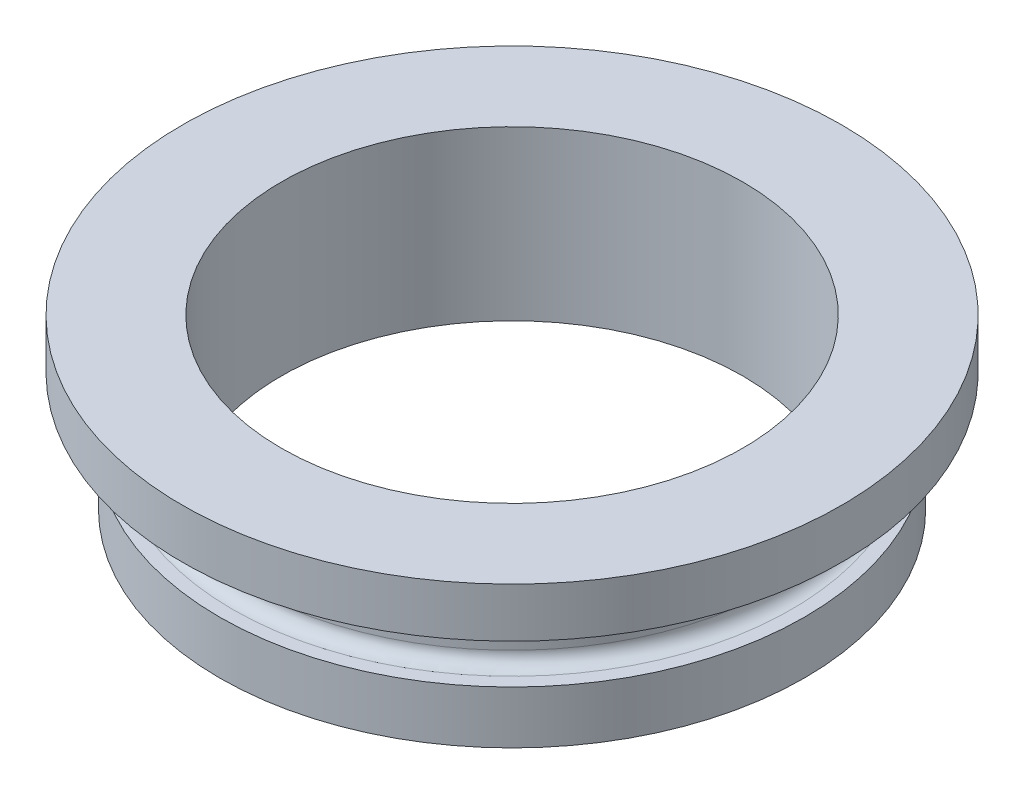
SolidWorks part; units mm, degrees
ref_plane "Front Plane" through (0, 0, 0) normal (0, 0, 1) x (1, 0, 0)
ref_plane "Top Plane" through (0, 0, 0) normal (0, 1, 0) x (1, 0, 0)
ref_plane "Right Plane" through (0, 0, 0) normal (1, 0, 0) x (0, 0, -1)
sketch "Sketch2" plane through (0, 0, 0) normal (0, 1, 0) x (1, 0, 0)
  circle A0 centre (0, 0) radius 56.3562
  dimension "D1" = 112.7125
extrude "Boss-Extrude1" add sketch "Sketch2" along normal blind 22.86
sketch "Sketch3" plane through (0, 22.86, 0) normal (0, 1, 0) x (1, 0, 0)
  circle A0 centre (0, 0) radius 63.5
extrude "Boss-Extrude2" add sketch "Sketch3" along normal blind 9.525
sketch "Sketch4" plane through (0, 0, 0) normal (0, -1, 0) x (1, 0, 0)
  circle A0 centre (0, 0) radius 44.45
extrude "Cut-Extrude1" cut sketch "Sketch4" against normal through all contours A0
sketch "Sketch9" plane through (0, 0, 0) normal (1, 0, 0) x (0, 0, -1)
  line L0 (-63.5, 22.86) -> (63.5, 22.86) construction
  line L1 (56.3562, 22.86) -> (51.2762, 22.86)
  line L2 (56.3562, 22.86) -> (56.3562, 10.16)
  line L3 (56.3562, 10.16) -> (51.2762, 10.16)
  line L4 (51.2762, 22.86) -> (51.2762, 10.16)
  line L5 (-56.3562, 22.86) -> (56.3562, 22.86) construction
  line L6 (0, 0) -> (0, 52.7802) construction
  dimension "D1" = 5.08
  dimension "D2" = 12.7
revolve "Cut-Revolve1" cut sketch "Sketch9" angle 360 about L6
fillet "Fillet1" radius 2.54 2 edges at (0, 10.16, -51.2762) (0, 22.86, -51.2762)
